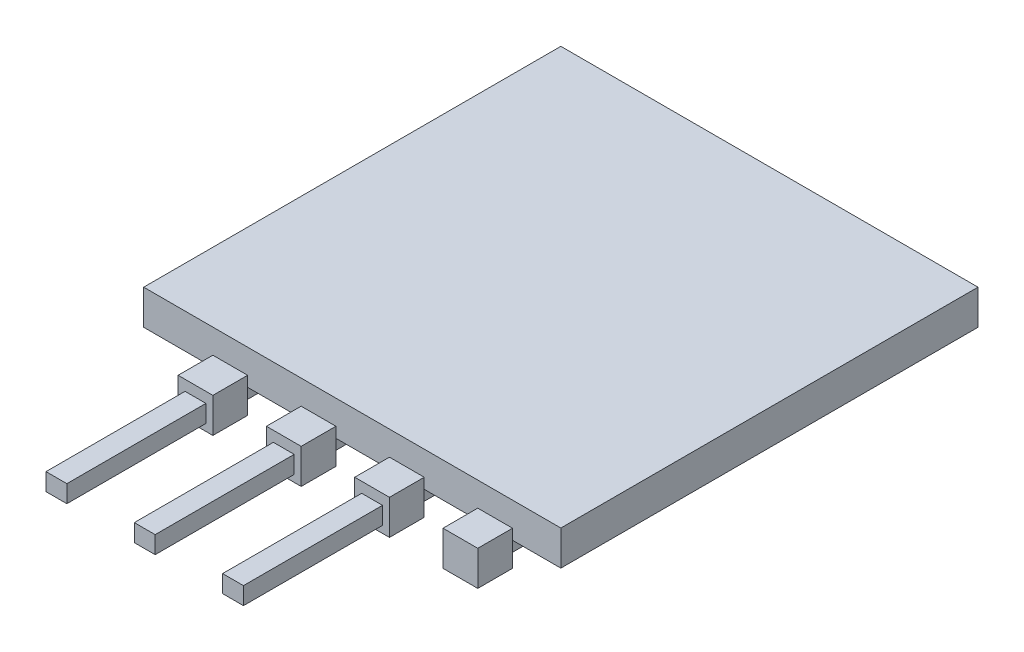
SolidWorks part; units mm, degrees
ref_plane "Front Plane" through (0, 0, 0) normal (0, 0, 1) x (1, 0, 0)
ref_plane "Top Plane" through (0, 0, 0) normal (0, 1, 0) x (1, 0, 0)
ref_plane "Right Plane" through (0, 0, 0) normal (1, 0, 0) x (0, 0, -1)
sketch "Sketch1" plane through (0, 0, 0) normal (0, 1, 0) x (1, 0, 0)
  line L1 (6, -6) -> (-6, -6)
  line L2 (6, -6) -> (6, 6)
  line L3 (6, 6) -> (-6, 6)
  line L4 (-6, -6) -> (-6, 6)
  line L5 (6, -6) -> (-6, 6) construction
  line L6 (6, 6) -> (-6, -6) construction
  point P0 (0, 0)
  dimension "D1" = 12
  dimension "D2" = 12
extrude "Boss-Extrude1" add sketch "Sketch1" along normal blind 1
sketch "Sketch2" plane through (0, 0, 6) normal (0, 0, 1) x (1, 0, 0)
  line L7 (-6, 1) -> (-6, 0) construction
  line L12 (-6, 0) -> (6, 0) construction
  line L13 (-3.81, 0) -> (-3.21, 0)
  line L14 (-3.81, 0) -> (-3.81, -0.5)
  line L15 (-3.81, -0.5) -> (-3.21, -0.5)
  line L16 (-3.21, 0) -> (-3.21, -0.5)
  dimension "D2" = 2.19
  dimension "D3" = 0.6
  dimension "D4" = 0.5
extrude "Boss-Extrude2" add sketch "Sketch2" along normal blind 5
extrude "Boss-Extrude3" add sketch "Sketch2<3>" against normal blind 2
sketch "Sketch2<3>" plane through (0, 0, 6) normal (0, 0, 1) x (1, 0, 0) same geometry as "Sketch2"
pattern_linear "LPattern2" count 4 spacing 2.54 along (1, 0, 0) of "Boss-Extrude3"
pattern_linear "LPattern3" count 3 spacing 2.54 along (1, 0, 0) of "Boss-Extrude2"
sketch "Sketch3" plane through (0, 0, 6) normal (0, 0, 1) x (1, 0, 0)
  line L0 (3.81, -0.5) -> (4.41, -0.5) construction
  line L1 (4.61, -0.7) -> (3.61, -0.7)
  line L2 (4.61, -0.7) -> (4.61, 0.3)
  line L3 (4.61, 0.3) -> (3.61, 0.3)
  line L4 (3.61, -0.7) -> (3.61, 0.3)
  line L5 (4.41, -0.5) -> (4.41, 0) construction
  dimension "D1" = 1
  dimension "D2" = 1
  dimension "D3" = 0.2
  dimension "D4" = 0.2
extrude "Boss-Extrude4" add sketch "Sketch3" along normal blind 1
pattern_linear "LPattern4" count 4 spacing 2.54 along (-1, 0, 0) of "Boss-Extrude4"
